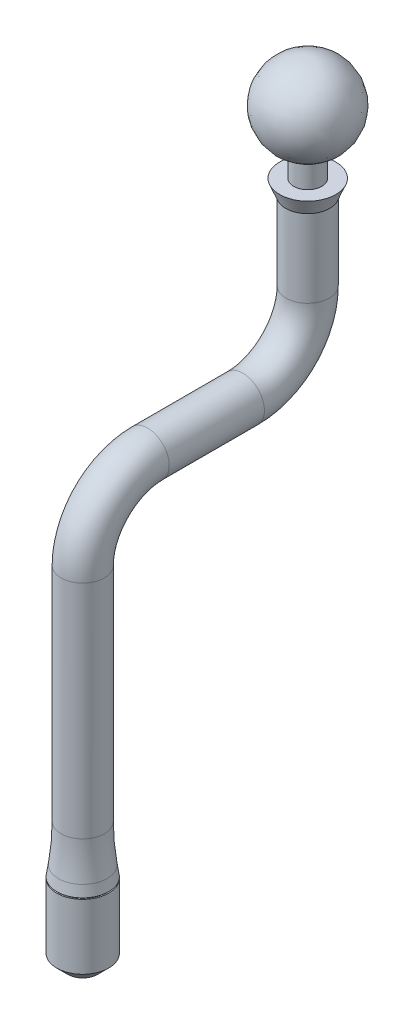
SolidWorks part; units mm, degrees
ref_plane "Front Plane" through (0, 0, 0) normal (0, 0, 1) x (1, 0, 0)
ref_plane "Top Plane" through (0, 0, 0) normal (0, 1, 0) x (1, 0, 0)
ref_plane "Right Plane" through (0, 0, 0) normal (1, 0, 0) x (0, 0, -1)
sketch "Sketch2" plane through (0, 0, 0) normal (1, 0, 0) x (0, 0, -1)
  line L0 (0, 0) -> (0, 18)
  line L1 (-37, -15) -> (-15, -15)
  line L2 (-52, -30) -> (-52, -85)
  arc A0 (0, 0) -> (-15, -15) centre (-15, 0) cw
  arc A1 (-37, -15) -> (-52, -30) centre (-37, -30) ccw
  dimension "D2" = 15
  dimension "D1" = 18
  dimension "D3" = 52
  dimension "D4" = 55
sweep "Sweep1" add path "Sketch2" circular profile diameter 10 parameters "D3"=10
sketch "Sketch11" plane through (0, -85, 0) normal (0, -1, 0) x (1, 0, 0)
  circle A0 centre (0, 52) radius 5
ref_plane "Plane1" through (0, -92.3, 0) normal (0, -1, 0) x (-1, 0, 0)
sketch "Sketch12" plane through (0, -92.3, 0) normal (0, -1, 0) x (-1, 0, 0)
  circle A0 centre (0, -52) radius 6
  dimension "D1" = 12
loft "Loft1" add profiles "Sketch11", "Sketch12" connector at (0, -85, 47) connector at (1.5205, -92.3, 46.1959)
fillet "Fillet1" radius 60 1 edges at (0, -85, 47)
sketch "Sketch13" plane through (0, -92.3, 0) normal (0, -1, 0) x (1, 0, 0)
  circle A0 centre (0, 52) radius 5.7
  dimension "D1" = 11.4
extrude "Boss-Extrude1" add sketch "Sketch13" along normal blind 0.3
sketch "Sketch14" plane through (0, -92.6, 0) normal (0, -1, 0) x (1, 0, 0)
  circle A0 centre (0, 52) radius 6
  circle A1 centre (0, 52) radius 5.7 construction
  dimension "D1" = 12
extrude "Boss-Extrude2" add sketch "Sketch14" along normal blind 15
ref_plane "Plane2" through (0, -110.1, 0) normal (0, -1, 0) x (-1, 0, 0)
sketch "Sketch15" plane through (0, -110.1, 0) normal (0, -1, 0) x (-1, 0, 0)
  circle A0 centre (0, -52) radius 3.5
  circle A1 centre (0, -52) radius 6 construction
  dimension "D1" = 7
sketch "Sketch16" plane through (0, -107.6, 0) normal (0, -1, 0) x (1, 0, 0)
  circle A0 centre (0, 52) radius 6
  circle A1 centre (0, 52) radius 6 construction
  dimension "D1" = 12
loft "Loft2" add profiles "Sketch15", "Sketch16" connector at (0, -110.1, 48.5) connector at (0, -107.6, 46)
sketch "Sketch18" plane through (0, 0, 0) normal (1, 0, 0) x (0, 0, -1)
  line L2 (6.5, 21.5) -> (5.0783, 18)
  line L3 (0, 18) -> (5.0783, 18)
  line L4 (0, 18) -> (0, 21.5)
  line L5 (5, 18) -> (-5, 18) construction
  line L6 (3.25, 21.5) -> (6.5, 21.5)
  line L7 (3.25, 21.5) -> (3.25, 27.059)
  line L8 (0, 21.5) -> (0, 45.5884)
  arc A0 (3.25, 27.059) -> (0, 45.5884) centre (0.4, 36.1088) ccw
  dimension "D1" = 6.5
  dimension "D2" = 3.5
sketch "Sketch19" plane through (0, 0, 0) normal (1, 0, 0) x (0, 0, -1)
  line L0 (0, 0) -> (0, 29.6018) construction
revolve "Revolve1" add sketch "Sketch18" angle 360 about L0
sketch "Sketch20" plane through (0, 0, 0) normal (1, 0, 0) x (0, 0, -1)
  line L0 (0, 0) -> (0, 18)
  line L1 (-37, -15) -> (-15, -15)
  line L2 (-52, -30) -> (-52, -92.6)
  arc A0 (0, 0) -> (-15, -15) centre (-15, 0) cw
  arc A1 (-37, -15) -> (-52, -30) centre (-37, -30) ccw
  point P8 (-52, -119.4455)
  point P9 (-52, -92.6)
  dimension "D2" = 15
  dimension "D1" = 18
  dimension "D3" = 52
sketch "Sketch17" plane through (0, -92.3, 0) normal (0, -1, 0) x (1, 0, 0)
  circle A0 centre (0, 52) radius 2
  circle A1 centre (0, 52) radius 3.5 construction
  dimension "D1" = 4
sweep "Cut-Sweep3" cut profiles "Sketch17" path "Sketch20"
sketch "Sketch22" plane through (0, 0, 0) normal (1, 0, 0) x (0, 0, -1)
  line L0 (-52, -110.1) -> (-52, -92.3)
  line L3 (-55.5, -110.1) -> (-48.5, -110.1) construction
  line L4 (-50, -92.3) -> (-54, -92.3) construction
  line L5 (-52, -92.3) -> (-49.2695, -92.3)
  line L6 (-57.7, -92.3) -> (-46.3, -92.3) construction
  line L7 (-49.2695, -92.3) -> (-49.2695, -95.7274)
  line L8 (-49.2695, -95.7274) -> (-46.8075, -95.7274)
  line L9 (-46.8075, -95.7274) -> (-46.8075, -107.1378)
  line L10 (-46.8075, -107.1378) -> (-49.34, -109.6703)
  line L11 (-49.34, -109.6703) -> (-51.25, -109.6703)
  line L12 (-51.25, -109.6703) -> (-51.25, -110.1)
  line L13 (-51.25, -110.1) -> (-52, -110.1)
  line L14 (-48.5, -110.1) -> (-46, -107.6) construction
  dimension "D1" = 0.75
revolve "Cut-Revolve1" cut sketch "Sketch22" angle 360 about L0
